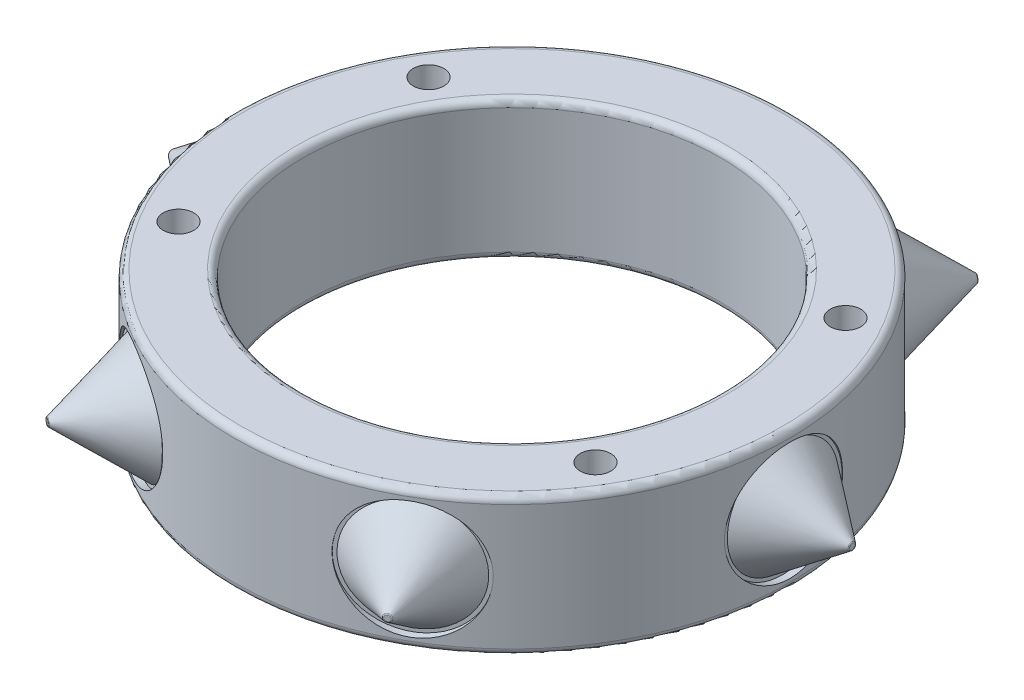
SolidWorks part; units mm, degrees
material "ABS"
ref_plane "正面" through (0, 0, 0) normal (0, 0, 1) x (1, 0, 0)
ref_plane "平面" through (0, 0, 0) normal (0, 1, 0) x (1, 0, 0)
ref_plane "右側面" through (0, 0, 0) normal (1, 0, 0) x (0, 0, -1)
sketch "ｽｹｯﾁ1" plane through (0, 0, 0) normal (0, 1, 0) x (1, 0, 0)
  circle A0 centre (0, 0) radius 20
  circle A1 centre (0, 0) radius 15
  dimension "D1" = 30
  dimension "D2" = 40
extrude "ﾎﾞｽ - 押し出し1" add sketch "ｽｹｯﾁ1" along normal blind 5 and the other way blind 5
fillet "ﾌｨﾚｯﾄ1" radius 0.5 4 edges at (0, -5, 15) (0, -5, 20) (0, 5, 15) (0, 5, 20)
sketch "ｽｹｯﾁ2" plane through (0, 0, 0) normal (0, 0, 1) x (1, 0, 0)
  line L0 (24.46, 0.28) -> (19.5, 4)
  line L1 (19.5, 4) -> (19.5, 0)
  line L2 (19.5, 0) -> (24.5, 0) construction
  line L4 (-20, 4.5) -> (20, 4.5) construction
  line L5 (-20, 4.5) -> (20, 4.5) construction
  line L6 (24.5, 0) -> (19.5, 0)
  line L7 (24.5, 0) -> (24.5, 0.2)
  arc A0 (24.5, 0.2) -> (24.46, 0.28) centre (24.4, 0.2) ccw
  point P4 (24.5, 0.25)
  dimension "D5" = 0.1
  dimension "D1" = 0.5
  dimension "D2" = 4
  dimension "D3" = 5
  dimension "D4" = 0.25
revolve "回転1" add sketch "ｽｹｯﾁ2" angle 360 about L6 region at (21.2646, 1.3383, 0)
ref_axis "軸1" through (0, -4.5, 0) along (0, 1, 0)
pattern_circular "円形ﾊﾟﾀｰﾝ5" count 6 over 360 about axis through (0, -4.5, 0) along (0, 1, 0) of bodies 102
sketch "ｽｹｯﾁ3" plane through (-9.75, 0, 16.8875) normal (0.5, 0, -0.866) x (-0.866, 0, -0.5)
  circle A0 centre (0, 0) radius 4.25
  dimension "D1" = 8.5
extrude "ｶｯﾄ - 押し出し1" cut sketch "ｽｹｯﾁ3" against normal blind 10
pattern_circular "円形ﾊﾟﾀｰﾝ6" count 6 over 360 about axis through (0, -4.5, 0) along (0, 1, 0) of "ｶｯﾄ - 押し出し1"
sketch "ｽｹｯﾁ4" plane through (0, 5, 0) normal (0, 1, 0) x (1, 0, 0)
  line L0 (0, 0) -> (34.9885, 0) construction
  line L1 (0, 0) -> (0, 31.4093) construction
  circle A0 centre (0, 0) radius 17.5 construction
  circle A1 centre (15.0083, 9) radius 1.1
  circle A2 centre (15.0083, -9) radius 1.1
  circle A3 centre (-15.0083, -9) radius 1.1
  circle A4 centre (-15.0083, 9) radius 1.1
  dimension "D1" = 35
  dimension "D2" = 2.2
  dimension "D3" = 9
extrude "ｶｯﾄ - 押し出し2" cut sketch "ｽｹｯﾁ4" against normal through all
